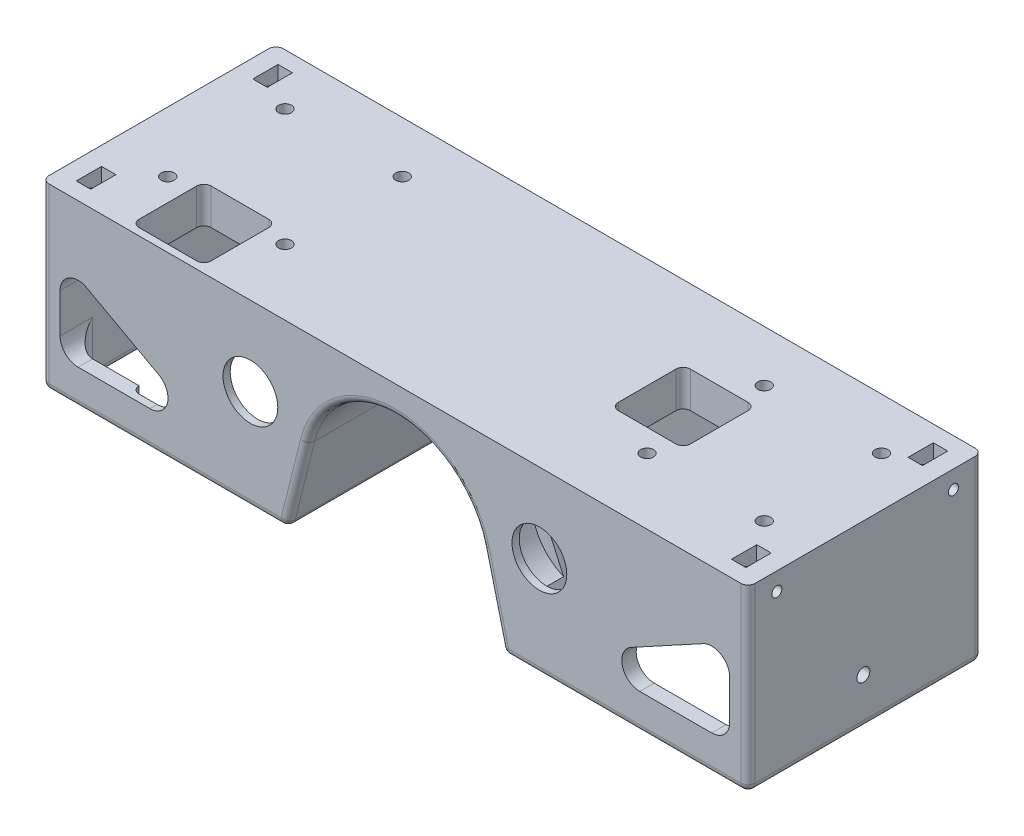
SolidWorks part; units mm, degrees
ref_plane "Front Plane" through (0, 0, 0) normal (0, 0, 1) x (1, 0, 0)
ref_plane "Top Plane" through (0, 0, 0) normal (0, 1, 0) x (1, 0, 0)
ref_plane "Right Plane" through (0, 0, 0) normal (1, 0, 0) x (0, 0, -1)
sketch "Sketch1" plane through (0, 0, 0) normal (0, 1, 0) x (1, 0, 0)
  line L1 (-124.46, -47.625) -> (124.46, -47.625)
  line L2 (-124.46, -47.625) -> (-124.46, 34.925)
  line L3 (-124.46, 34.925) -> (124.46, 34.925)
  line L4 (124.46, -47.625) -> (124.46, 34.925)
  line L5 (-124.46, -47.625) -> (124.46, 34.925) construction
  line L6 (-124.46, 34.925) -> (124.46, -47.625) construction
  point P0 (0, 0)
  point P8 (0, -6.35)
  dimension "D1" = 82.55
  dimension "D2" = 248.92
  dimension "D3" = 6.35
extrude "Boss-Extrude1" add sketch "Sketch1" along normal mid plane 63.5
sketch "Sketch3" plane through (0, 0, 47.625) normal (0, 0, 1) x (1, 0, 0)
  line L0 (-48.1584, -19.05) -> (-118.0084, 19.05) construction
  line L1 (-118.0084, -31.75) -> (118.0084, -31.75)
  line L2 (-118.0084, -31.75) -> (-118.0084, 19.05)
  line L3 (-118.0084, 19.05) -> (118.0084, 19.05)
  line L4 (118.0084, -31.75) -> (118.0084, 19.05)
  line L5 (-124.46, 31.75) -> (124.46, 31.75) construction
  line L6 (-124.46, 31.75) -> (-124.46, -31.75) construction
  line L7 (-38.1, -31.75) -> (-30.8081, -2.4839)
  line L8 (0, 19.05) -> (0, -31.75) construction
  line L9 (-48.1584, -19.05) -> (-32.9184, 19.05)
  line L10 (-45.7833, -13.1123) -> (-104.7475, 19.05)
  line L11 (-61.4193, -19.05) -> (-118.0084, 11.8168)
  line L12 (-45.1177, -13.4754) -> (-114.9677, 24.6246) construction
  line L13 (-124.46, -31.75) -> (124.46, -31.75) construction
  line L14 (-118.0084, -19.05) -> (-48.1584, -19.05)
  line L15 (-118.0084, -31.75) -> (0, -31.75)
  line L16 (-51.1991, -24.6246) -> (-121.0491, 13.4754) construction
  line L17 (61.4193, -19.05) -> (118.0084, 11.8168)
  line L18 (45.7833, -13.1123) -> (104.7475, 19.05)
  line L19 (48.1584, -19.05) -> (32.9184, 19.05)
  line L20 (118.0084, -19.05) -> (48.1584, -19.05)
  line L21 (38.1, -31.75) -> (30.8081, -2.4839)
  circle A0 centre (0, -10.16) radius 31.75
  point P6 (0, 19.05)
  line M5 (-124.46, -31.75) -> (124.46, -31.75)
  dimension "D3" = 63.5
  dimension "D1" = 12.7
  dimension "D2" = 6.4516
  dimension "D4" = 85.09
  dimension "D5" = 12.7
  dimension "D6" = 38.1
  dimension "D9" = 69.85
  dimension "D10" = 10.16
  dimension "D7" = 6.35
  dimension "D8" = 6.35
extrude "Cut-Extrude2" cut sketch "Sketch3" against normal through all contours L2 L14 L11 | L20 L4 L17 | L1 L3 | A0 L7 L1 M5 | A0 L21 M5 | L3 A0 region at (-31.9636, -24.5217, 47.625) region at (-99.1454, -8.7611, 47.625) region at (0, -7.6125, 47.625) region at (31.9636, -24.5217, 47.625) region at (0, 20.0696, 47.625) region at (99.1454, -8.7611, 47.625)
sketch "Sketch4" plane through (0, 31.75, 0) normal (0, 1, 0) x (1, 0, 0)
  line L1 (-95.25, -45.085) -> (-69.85, -45.085)
  line L2 (-95.25, -45.085) -> (-95.25, -19.685)
  line L3 (-95.25, -19.685) -> (-69.85, -19.685)
  line L4 (-69.85, -45.085) -> (-69.85, -19.685)
  line L5 (-103.2046, -24.4646) -> (-82.55, -3.81) construction
  line L10 (65.7054, -24.4646) -> (86.36, -3.81) construction
  line L12 (45.085, 8.89) -> (70.485, 8.89)
  line L13 (45.085, 8.89) -> (45.085, -16.51)
  line L14 (45.085, -16.51) -> (70.485, -16.51)
  line L15 (70.485, 8.89) -> (70.485, -16.51)
  circle A0 centre (-103.2046, -24.4646) radius 2.286
  circle A1 centre (-103.2046, 16.8446) radius 2.286
  circle A2 centre (-61.8954, 16.8446) radius 2.286
  circle A3 centre (-61.8954, -24.4646) radius 2.286
  circle A4 centre (65.7054, -24.4646) radius 2.286
  circle A8 centre (65.7054, 16.8446) radius 2.286
  circle A9 centre (107.0146, 16.8446) radius 2.286
  circle A10 centre (107.0146, -24.4646) radius 2.286
  point P8 (-82.55, -3.81)
  point P11 (-82.55, -19.685)
  point P12 (70.485, -3.81)
  point P21 (-82.55, -3.81)
  point P26 (86.36, -3.81)
  point P35 (86.36, -3.81)
  point P38 (86.36, -3.81)
  dimension "D6" = 4.572
  dimension "D13" = 4.572
  dimension "D1" = 45
  dimension "D2" = 25.4
  dimension "D3" = 25.4
  dimension "D4" = 82.55
  dimension "D5" = 29.21
  dimension "D7" = 15.875
  dimension "D9" = 45
  dimension "D10" = 15.875
  dimension "D11" = 25.4
  dimension "D12" = 29.21
  dimension "D14" = 25.4
  dimension "D15" = 86.36
  dimension "D17" = 3.81
  dimension "D18" = 3.81
  dimension "D19" = 41.3092
  dimension "D8" = 4
  dimension "D16" = 4
sketch "Sketch5" plane through (0, 0, 0) normal (0, 0, 1) x (1, 0, 0)
  line L0 (-48.26, -31.75) -> (-38.1, -31.75)
  line L2 (-118.0084, 19.05) -> (-118.0084, -31.75)
  line L3 (-118.0084, -31.75) -> (-38.1, -31.75)
  line L4 (118.0084, 19.05) -> (118.0084, -31.75)
  line L6 (38.1, -31.75) -> (124.46, -31.75) construction
  line L7 (118.0084, -19.05) -> (118.0084, 11.8168) construction
  line L8 (-118.0084, -19.05) -> (-118.0084, 11.8168) construction
  line L10 (-48.26, -21.59) -> (-48.26, -31.75)
  line L11 (-48.26, -21.59) -> (-31.6484, 15.24)
  line L18 (38.1, -31.75) -> (118.0084, -31.75)
  line L19 (0, 31.75) -> (0, -31.75) construction
  line L21 (48.26, -21.59) -> (31.6484, 15.24)
  line L22 (48.26, -21.59) -> (48.26, -31.75)
  line L24 (48.26, -31.75) -> (38.1, -31.75)
  line L25 (-118.0084, 19.05) -> (-31.6484, 19.05)
  line L26 (30.8081, -2.4839) -> (38.1, -31.75)
  line L27 (-30.8081, -2.4839) -> (-38.1, -31.75)
  line L28 (-30.8081, -2.4839) -> (-38.1, -31.75)
  line L29 (118.0084, 19.05) -> (31.6484, 19.05)
  line L30 (-124.46, 31.75) -> (124.46, 31.75) construction
  line L31 (-31.6484, 19.05) -> (-31.6484, 15.24)
  line L32 (31.6484, 19.05) -> (31.6484, 15.24)
  arc A1 (30.8081, -2.4839) -> (-30.8081, -2.4839) centre (0, -10.16) ccw construction
  arc A2 (0, 21.59) -> (30.8081, -2.4839) centre (0, -10.16) cw
  arc A3 (30.8081, -2.4839) -> (-30.8081, -2.4839) centre (0, -10.16) ccw
  arc A4 (0, 21.59) -> (-30.8081, -2.4839) centre (0, -10.16) ccw
  arc A5 (30.8081, -2.4839) -> (-30.8081, -2.4839) centre (0, -10.16) ccw
  dimension "D1" = 10.16
  dimension "D2" = 86.36
  dimension "D3" = 10.16
  dimension "D5" = 50.8
  dimension "D6" = 3.81
  dimension "D4" = 0
extrude "Cut-Extrude4" cut sketch "Sketch5" against normal offset from surface 5.08 and the other way offset from surface 5.08 contours L10 L11 L2 L3 | L3 L4 region at (79.276, -5.2417, 0) region at (-79.276, -5.2417, 0) up to face at (99.1454, -8.7611, -34.925) other way up to face at (99.1454, -8.7611, 47.625)
extrude "Cut-Extrude3" cut sketch "Sketch4" against normal through all
sketch "Sketch8" plane through (0, 0, -34.925) normal (0, 0, 1) x (1, 0, 0)
  line L0 (-45.8404, -19.05) -> (-118.11, 19.05) construction
  line L1 (-118.11, -31.75) -> (118.11, -31.75)
  line L2 (-118.11, -31.75) -> (-118.11, 19.05)
  line L3 (-118.11, 19.05) -> (118.11, 19.05)
  line L4 (118.11, -31.75) -> (118.11, 19.05)
  line L5 (-36.83, -31.75) -> (-19.05, 19.05)
  line L6 (0, 19.05) -> (0, -31.75) construction
  line L7 (-45.8404, -19.05) -> (-32.5054, 19.05)
  line L8 (-43.7193, -12.9898) -> (-102.459, 19.05)
  line L9 (-61.4193, -19.05) -> (-118.11, 11.8722)
  line L10 (-118.11, -19.05) -> (-45.8404, -19.05)
  line L11 (-118.11, -31.75) -> (-36.83, -31.75)
  line L12 (61.4193, -19.05) -> (118.11, 11.8722)
  line L13 (43.7193, -12.9898) -> (102.459, 19.05)
  line L14 (45.8404, -19.05) -> (32.5054, 19.05)
  line L15 (118.11, -19.05) -> (45.8404, -19.05)
  line L16 (36.83, -31.75) -> (19.05, 19.05)
  line L17 (-124.46, 31.75) -> (-124.46, -31.75) construction
  line L18 (-124.46, 31.75) -> (124.46, 31.75) construction
  line L19 (124.46, 31.75) -> (124.46, -31.75) construction
  line L20 (-124.46, -31.75) -> (-38.1, -31.75) construction
  line L21 (-61.4193, -19.05) -> (-118.0084, 11.8168) construction
  point P5 (0, 19.05)
  dimension "D1" = 12.7
  dimension "D2" = 19.05
  dimension "D3" = 12.7
  dimension "D4" = 36.83
  dimension "D5" = 6.35
  dimension "D6" = 12.7
  dimension "D7" = 6.35
  dimension "D8" = 6.35
extrude "Cut-Extrude7" cut sketch "Sketch8" along normal blind 5.08 contours L13 L14 L3 | L7 L8 L3 region at (-59.5612, 8.3701, -34.925) region at (59.5612, 8.3701, -34.925)
fillet "Fillet2" radius 6.35 26 edges at (-118.0084, 15.4334, 42.545) (-118.0084, -25.4, 42.545) (-118.0084, -19.05, 45.085) (-118.0084, 11.8168, 45.085) (-61.4193, -19.05, 45.085) (118.0084, 15.4334, 42.545) (118.0084, -19.05, 45.085) (118.0084, 11.8168, 45.085) (61.4193, -19.05, 45.085) (118.0084, -25.4, -29.845) (118.0084, 15.4334, -29.845) (118.0084, -19.05, -32.385) (118.0084, 11.8168, -32.385) (61.4193, -19.05, -32.385) (-61.4193, -19.05, -32.385) (-118.0084, -19.05, -32.385) (-118.0084, -25.4, -29.845) (-118.0084, 15.4334, -29.845) (-118.0084, 11.8168, -32.385) (118.0084, -25.4, 42.545) (43.7193, -12.9898, -32.385) (102.459, 19.05, -32.385) (32.5054, 19.05, -32.385) (-32.5054, 19.05, -32.385) (-43.7193, -12.9898, -32.385) (-102.459, 19.05, -32.385)
fillet "Fillet4" radius 1.27 4 edges at (-48.26, -26.67, -29.845) (-48.26, -26.67, 42.545) (48.26, -26.67, 42.545) (48.26, -26.67, -29.845)
fillet "Fillet5" radius 2.54 11 edges at (45.085, 25.4, 16.51) (45.085, 25.4, -8.89) (70.485, 25.4, -8.89) (70.485, 25.4, 16.51) (-69.85, 0, 45.085) (-69.85, 25.4, 19.685) (-95.25, 25.4, 19.685) (-95.25, 15.5766, 45.085) (45.085, -23.1503, 16.51) (45.085, -23.1503, -8.89) (-95.25, -25.4, 45.085)
sketch "Sketch6" plane through (0, 0, 47.625) normal (0, 0, -1) x (-1, 0, 0)
  line L0 (0, 0) -> (0, 31.75) construction
  line L1 (-124.46, 31.75) -> (124.46, 31.75) construction
  circle A0 centre (-50.927, 3.81) radius 9.652
  circle A1 centre (50.927, 3.81) radius 9.652
  dimension "D1" = 19.304
extrude "Cut-Extrude5" cut sketch "Sketch6" along normal blind 5.08
sketch "Sketch7" plane through (0, 0, 45.085) normal (0, 0, 1) x (1, 0, 0)
  line L0 (0, 0) -> (0, -31.75) construction
  line L8 (124.46, -31.75) -> (38.1, -31.75) construction
  circle A0 centre (50.927, 3.81) radius 17.78
  circle A2 centre (-50.927, 3.81) radius 17.78
  dimension "D1" = 35.56
extrude "Cut-Extrude6" cut sketch "Sketch7" against normal blind 12.7
sketch "Sketch9" plane through (0, 19.05, 0) normal (0, -1, 0) x (1, 0, 0)
  circle A0 centre (-103.2046, 24.4646) radius 5.08
  circle A1 centre (-103.2046, -16.8446) radius 5.08
  circle A2 centre (-61.8954, -16.8446) radius 5.08
  circle A3 centre (-61.8954, 24.4646) radius 5.08
  circle A4 centre (65.7054, 24.4646) radius 5.08
  circle A5 centre (107.0146, 24.4646) radius 5.08
  circle A6 centre (107.0146, -16.8446) radius 5.08
  circle A7 centre (65.7054, -16.8446) radius 5.08
  dimension "D1" = 10.16
extrude "Cut-Extrude8" cut sketch "Sketch9" against normal blind 7.62
fillet "Fillet7" radius 2.54 6 edges at (34.4541, -17.117, -34.925) (0, 21.59, -34.925) (34.4541, -17.117, 47.625) (0, 21.59, 47.625) (-34.4541, -17.117, -34.925) (-34.4541, -17.117, 47.625)
sketch "Sketch10" plane through (124.46, 0, 0) normal (1, 0, 0) x (0, 0, -1)
  line L0 (-47.625, 31.75) -> (34.925, 31.75) construction
  line L1 (-47.625, 31.75) -> (-47.625, -31.75) construction
  line L2 (34.925, 31.75) -> (34.925, -31.75) construction
  circle A0 centre (-6.985, -15.24) radius 2.286
  circle A1 centre (-37.465, 25.4) radius 1.778
  circle A2 centre (24.765, 25.4) radius 1.778
  dimension "D1" = 4.572
  dimension "D3" = 3.556
  dimension "D2" = 6.35
  dimension "D4" = 10.16
  dimension "D5" = 10.16
extrude "Cut-Extrude9" cut sketch "Sketch10" against normal blind 25.4
fillet "Fillet8" radius 2.54 40 edges at (-94.5061, -31.75, 44.3411) (-70.5939, -31.75, 44.3411) (45.8289, -31.75, -8.1461) (45.8289, -31.75, 15.7661) (-103.4542, -31.75, 42.545) (-116.1485, -31.75, 40.6851) (-118.0084, -31.75, 6.35) (-116.1485, -31.75, -27.9851) (-80.5942, -31.75, -29.845) (-48.632, -31.75, -29.473) (-59.69, -31.75, 42.545) (-48.632, -31.75, 42.173) (48.26, -31.75, -18.7325) (48.632, -31.75, -29.473) (80.5942, -31.75, -29.845) (116.1485, -31.75, -27.9851) (48.26, -31.75, 28.8925) (48.632, -31.75, 42.173) (80.5942, -31.75, 42.545) (116.1485, -31.75, 40.6851) (-82.5888, -31.75, 47.625) (-38.8667, -31.75, 46.8811) (-38.1, -31.75, 6.35) (-38.8667, -31.75, -34.1811) (82.5888, -31.75, -34.925) (38.8667, -31.75, -34.1811) (38.1, -31.75, 6.35) (38.8667, -31.75, 46.8811) (-82.55, -31.75, 45.085) (45.085, -31.75, 3.81) (-48.26, -31.75, 6.35) (118.0084, -31.75, 6.35) (124.46, -31.75, 6.35) (-124.46, -31.75, 6.35) (-124.46, 0, 47.625) (-82.5888, -31.75, -34.925) (-124.46, 0, -34.925) (82.5888, -31.75, 47.625) (124.46, 0, 47.625) (124.46, 0, -34.925)
sketch "Sketch12" plane through (118.0084, 0, 0) normal (-1, 0, 0) x (0, 0, 1)
  line L0 (45.085, 31.75) -> (-32.385, 31.75) construction
  line L1 (33.02, 19.05) -> (41.91, 19.05)
  line L2 (33.02, 19.05) -> (33.02, 31.75)
  line L3 (33.02, 31.75) -> (41.91, 31.75)
  line L4 (41.91, 19.05) -> (41.91, 31.75)
  line L5 (33.02, 19.05) -> (41.91, 31.75) construction
  line L6 (33.02, 31.75) -> (41.91, 19.05) construction
  line L8 (-20.32, 19.05) -> (-29.21, 19.05)
  line L9 (-20.32, 19.05) -> (-20.32, 31.75)
  line L10 (-20.32, 31.75) -> (-29.21, 31.75)
  line L11 (-29.21, 19.05) -> (-29.21, 31.75)
  line L12 (-20.32, 19.05) -> (-29.21, 31.75) construction
  line L13 (-20.32, 31.75) -> (-29.21, 19.05) construction
  point P0 (37.465, 25.4)
  point P8 (-24.765, 25.4)
  dimension "D1" = 8.89
  dimension "D2" = 8.89
extrude "Cut-Extrude10" cut sketch "Sketch12" along normal blind 5.08
mirror "Mirror1" about plane through (0, 0, 0) normal (1, 0, 0) of "Cut-Extrude9", "Cut-Extrude10"
sketch "Sketch13" plane through (0, 0, -34.925) normal (0, 0, -1) x (-1, 0, 0)
  circle A0 centre (-43.307, -24.765) radius 1.778
  circle A1 centre (43.053, -24.765) radius 1.778
  circle A2 centre (-25.527, 19.685) radius 1.778
  circle A4 centre (25.273, 19.685) radius 1.778
  dimension "D1" = 3.556
extrude "Cut-Extrude13" cut sketch "Sketch13" against normal blind 25.4
